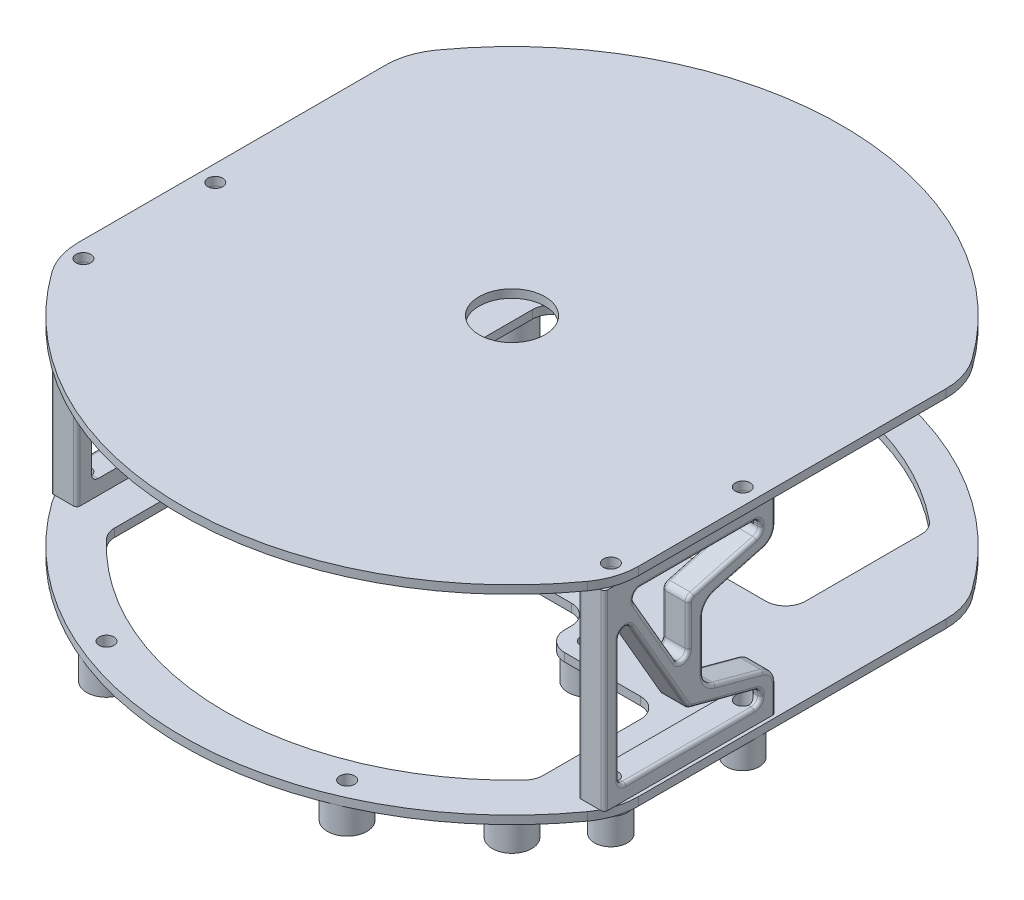
SolidWorks part; units mm, degrees
ref_plane "Front" through (0, 0, 0) normal (0, 0, 1) x (1, 0, 0)
ref_plane "Top" through (0, 0, 0) normal (0, 1, 0) x (1, 0, 0)
ref_plane "Right" through (0, 0, 0) normal (1, 0, 0) x (0, 0, -1)
sketch "Sketch1" plane through (0, 0, 0) normal (0, 1, 0) x (1, 0, 0)
  line L0 (0, 71.1393) -> (0, -87.7098) construction
  line L1 (-42.5, 26.3391) -> (-42.5, -26.3391)
  line L2 (42.5, 26.3391) -> (42.5, -26.3391)
  arc A0 (-42.5, -26.3391) -> (42.5, -26.3391) centre (0, 0) ccw
  arc A1 (42.5, 26.3391) -> (-42.5, 26.3391) centre (0, 0) ccw
  dimension "D1" = 100
  dimension "D2" = 85
extrude "Boss-Extrude1" add sketch "Sketch1" along normal blind 1.25
sketch "Sketch2" plane through (0, 0, 0) normal (0, -1, 0) x (1, 0, 0)
  line L0 (0, 45.5144) -> (0, -63.1722) construction
  line L1 (-51.2989, 0) -> (55.2567, 0) construction
  circle A0 centre (-33, 33) radius 3
  circle A2 centre (-33, 33) radius 1.125
  circle A4 centre (-33, -33) radius 1.125
  circle A5 centre (-33, -33) radius 3
  circle A6 centre (33, -33) radius 3
  circle A7 centre (33, -33) radius 1.125
  circle A8 centre (33, 33) radius 1.125
  circle A9 centre (33, 33) radius 3
  dimension "D3" = 2.25
  dimension "D4" = 6
  dimension "D1" = 66
  dimension "D2" = 66
extrude "Boss-Extrude2" add sketch "Sketch2" along normal blind 4
fillet "Fillet1" radius 10 4 edges at (-42.5, 0.625, -26.3391) (-42.5, 0.625, 26.3391) (42.5, 0.625, -26.3391) (42.5, 0.625, 26.3391)
sketch "Sketch3" plane through (0, 1.25, 0) normal (0, 1, 0) x (1, 0, 0)
  line L0 (0, 58.0627) -> (0, -62.1815) construction
  line L1 (-18.25, -6.75) -> (18.25, -6.75) construction
  line L2 (-18.25, -6.75) -> (-18.25, -43.25) construction
  line L3 (-18.25, -43.25) -> (18.25, -43.25) construction
  line L4 (18.25, -6.75) -> (18.25, -43.25) construction
  line L5 (-18.25, -6.75) -> (18.25, -43.25) construction
  line L6 (-18.25, -43.25) -> (18.25, -6.75) construction
  circle A0 centre (-18.25, -6.75) radius 1.125
  circle A1 centre (18.25, -6.75) radius 1.125
  circle A2 centre (18.25, -43.25) radius 1.125
  circle A3 centre (-18.25, -43.25) radius 1.125
  circle A4 centre (-40, -5) radius 1.125
  circle A5 centre (-40, -25) radius 1.125
  circle A6 centre (40, -25) radius 1.125
  circle A7 centre (40, -5) radius 1.125
  point P0 (0, -25)
  dimension "D1" = 2.25
  dimension "D2" = 36.5
  dimension "D3" = 25
  dimension "D4" = 20
  dimension "D5" = 80
  dimension "D6" = 0
sketch "Sketch4" plane through (0, 0, 0) normal (0, -1, 0) x (1, 0, 0)
  circle A0 centre (-18.25, 43.25) radius 3
  circle A1 centre (18.25, 43.25) radius 3
  circle A2 centre (18.25, 6.75) radius 3
  circle A3 centre (-18.25, 6.75) radius 3
  circle A4 centre (-40, 25) radius 2.5
  circle A5 centre (-40, 5) radius 2.5
  circle A6 centre (40, 25) radius 2.5
  circle A7 centre (40, 5) radius 2.5
  dimension "D1" = 6
  dimension "D2" = 5
extrude "Boss-Extrude3" add sketch "Sketch4" along normal up to surface (4 mm away) up to face at (-33, -4, 30)
extrude "Cut-Extrude1" cut sketch "Sketch3" against normal through all
sketch "Sketch6" plane through (0, 0, 0) normal (0, -1, 0) x (1, 0, 0)
  line L0 (-29.5, -33.9816) -> (-29.5, -12)
  line L1 (-29.5, -12) -> (-3.5, -12)
  line L2 (29.5, -12) -> (29.5, -33.9816)
  line L3 (0, 0) -> (0, -57.2909) construction
  line L4 (-32.5, 28.9137) -> (-32.5, 10)
  line L5 (-32.5, 10) -> (-15, 10)
  line L6 (32.5, 10) -> (32.5, 28.9137)
  line L7 (-3.5, -12) -> (-3.5, -44.8637)
  line L8 (3.5, -12) -> (3.5, -44.8637)
  line L9 (3.5, -12) -> (29.5, -12)
  line L10 (15, 10) -> (32.5, 10)
  line L12 (-15, 10) -> (-15, 3)
  line L13 (-15, 3) -> (15, 3)
  line L14 (15, 10) -> (15, 3)
  arc A0 (-29.5, -33.9816) -> (-3.5, -44.8637) centre (0, 0) ccw
  arc A1 (-40.625, -29.1481) -> (40.625, -29.1481) centre (0, 0) ccw construction
  arc A2 (-32.5, 28.9137) -> (32.5, 28.9137) centre (0, 0) cw
  arc A3 (40.625, 29.1481) -> (-40.625, 29.1481) centre (0, 0) ccw construction
  arc A4 (3.5, -44.8637) -> (29.5, -33.9816) centre (0, 0) ccw
  dimension "D2" = 5
  dimension "D4" = 6.5
  dimension "D1" = 59
  dimension "D3" = 12
  dimension "D5" = 10
  dimension "D6" = 7
  dimension "D7" = 65
  dimension "D8" = 7
  dimension "D9" = 30
extrude "Cut-Extrude2" cut sketch "Sketch6" against normal through all
fillet "Fillet2" radius 3 16 edges at (-29.5, 0.625, -12) (-3.5, 0.625, -12) (-3.5, 0.625, -44.8637) (29.5, 0.625, -12) (29.5, 0.625, -33.9816) (3.5, 0.625, -44.8637) (3.5, 0.625, -12) (-29.5, 0.625, -33.9816) (32.5, 0.625, 28.9137) (-32.5, 0.625, 28.9137) (-32.5, 0.625, 10) (32.5, 0.625, 10) (15, 0.625, 3) (15, 0.625, 10) (-15, 0.625, 3) (-15, 0.625, 10)
ref_point "Point1"
ref_plane "Plane1" through (-40, 0, 0) normal (-1, 0, 0) x (0, 0, 1)
sketch "Sketch7" plane through (-40, 0, 0) normal (-1, 0, 0) x (0, 0, 1)
  line L0 (2, 1.25) -> (2, 7.25)
  line L1 (-23.3184, 1.25) -> (23.3184, 1.25) construction
  line L2 (2, 7.25) -> (13, 10.1974)
  line L3 (13, 10.1974) -> (13, 21.3026)
  line L4 (13, 21.3026) -> (2, 24.25)
  line L5 (2, 24.25) -> (2, 30.25)
  line L6 (2, 30.25) -> (28, 30.25)
  line L7 (28, 30.25) -> (28, 1.25)
  line L8 (28, 1.25) -> (2, 1.25)
  line L9 (4.25, 28) -> (24.2157, 28)
  line L11 (25.75, 3.5) -> (4.25, 3.5)
  line L12 (4.25, 3.5) -> (4.25, 5.5235)
  line L13 (4.25, 5.5235) -> (15.25, 8.471)
  line L14 (15.25, 12.471) -> (15.25, 23.029)
  line L15 (15.25, 23.029) -> (4.25, 25.9765)
  line L16 (4.25, 25.9765) -> (4.25, 28)
  line L17 (15.25, 8.471) -> (25.75, 26.6575)
  line L19 (24.2157, 28) -> (15.25, 12.471)
  line L21 (15.25, 8.471) -> (15.25, 23.029) construction
  line L22 (25.75, 26.6575) -> (25.75, 3.5)
  line L23 (25.75, 28) -> (25.75, 3.5) construction
  line L24 (4.25, 28) -> (25.75, 28) construction
  dimension "D1" = 2
  dimension "D2" = 26
  dimension "D3" = 15
  dimension "D4" = 15
  dimension "D5" = 15
  dimension "D6" = 6
  dimension "D7" = 29
  dimension "D9" = 2
  dimension "D10" = 30
  dimension "D8" = 2.25
extrude "Boss-Extrude4" add sketch "Sketch7" along normal mid plane 4 separate body
fillet "Fillet3" radius 2.5 4 edges at (-40, 7.25, 2) (-40, 10.1974, 13) (-40, 21.3026, 13) (-40, 24.25, 2)
fillet "Fillet4" radius 1 10 edges at (-40, 26.6575, 25.75) (-40, 8.471, 15.25) (-40, 5.5235, 4.25) (-40, 3.5, 25.75) (-40, 3.5, 4.25) (-40, 12.471, 15.25) (-40, 28, 4.25) (-40, 25.9765, 4.25) (-40, 23.029, 15.25) (-40, 28, 24.2157)
fillet "Fillet5" radius 0.5 50 edges at (-38, 15.75, 28) (-38, 3.2908, 2) (-38, 6.8536, 2.5166) (-38, 8.7237, 7.5) (-38, 10.5939, 12.4834) (-38, 15.75, 13) (-38, 20.9061, 12.4834) (-38, 22.7763, 7.5) (-38, 24.6464, 2.5166) (-38, 28.2092, 2) (-42, 3.2908, 2) (-42, 6.8536, 2.5166) (-42, 8.7237, 7.5) (-42, 10.5939, 12.4834) (-42, 15.75, 13) (-42, 20.9061, 12.4834) (-42, 22.7763, 7.5) (-42, 24.6464, 2.5166) (-42, 28.2092, 2) (-42, 15.75, 28) (-42, 3.7929, 4.5429) (-42, 5.3649, 4.4566) (-42, 7.0429, 9.9205) (-42, 8.5363, 15.1998) (-42, 16.1276, 19.6705) (-42, 23.8914, 25.0088) (-42, 13.7127, 25.75) (-42, 3.7929, 25.4571) (-42, 3.5, 15) (-38, 27.7071, 4.5429) (-42, 27.7071, 4.5429) (-38, 26.1351, 4.4566) (-38, 24.5028, 9.75) (-38, 22.8705, 15.0434) (-38, 19.2324, 15.25) (-38, 15.2371, 15.9912) (-42, 26.1351, 4.4566) (-42, 24.5028, 9.75) (-42, 22.8705, 15.0434) (-42, 19.2324, 15.25) (-42, 15.2371, 15.9912) (-38, 28, 13.8668) (-42, 28, 13.8668) (-38, 21.1015, 20.2328) (-42, 21.1015, 20.2328) (-38, 27.5, 23.3497) (-42, 27.5, 23.3497) (-38, 26.8719, 4.25) (-42, 26.8719, 4.25) (-42, 4.6281, 4.25)
sketch "Sketch8" plane through (0, 1.25, 0) normal (0, -1, 0) x (1, 0, 0)
  circle A0 centre (-40, 5) radius 1.125 construction
  circle A1 centre (-40, 25) radius 1.125 construction
  circle A2 centre (-40, 5) radius 1.125
  circle A3 centre (-40, 25) radius 1.125
extrude "Cut-Extrude3" cut sketch "Sketch8" against normal blind 3.5
extrude "Cut-Extrude4" cut sketch "Sketch8<3>" along normal blind 3.5 from surface starting at face at (-40, 30.25, 15)
sketch "Sketch8<3>" plane through (0, 1.25, 0) normal (0, -1, 0) x (1, 0, 0) same geometry as "Sketch8"
mirror "Mirror1" about plane through (0, 0, 0) normal (1, 0, 0) of bodies 109
sketch "Sketch9" plane through (0, 30.25, 0) normal (0, 1, 0) x (1, 0, 0)
  line L0 (-42.5, 23.3184) -> (-42.5, -23.3184) construction
  line L1 (42.5, -23.3184) -> (42.5, 23.3184) construction
  line L2 (-42.5, 23.3184) -> (-42.5, -23.3184)
  line L3 (42.5, -23.3184) -> (42.5, 23.3184)
  arc A0 (40.625, 29.1481) -> (-40.625, 29.1481) centre (0, 0) ccw construction
  arc A1 (-40.625, 29.1481) -> (-42.5, 23.3184) centre (-32.5, 23.3184) ccw construction
  arc A2 (-42.5, -23.3184) -> (-40.625, -29.1481) centre (-32.5, -23.3184) ccw construction
  arc A3 (-40.625, -29.1481) -> (40.625, -29.1481) centre (0, 0) ccw construction
  arc A4 (40.625, -29.1481) -> (42.5, -23.3184) centre (32.5, -23.3184) ccw construction
  arc A5 (42.5, 23.3184) -> (40.625, 29.1481) centre (32.5, 23.3184) ccw construction
  arc A6 (-40.625, 29.1481) -> (-42.5, 23.3184) centre (-32.5, 23.3184) ccw
  arc A7 (-42.5, -23.3184) -> (-40.625, -29.1481) centre (-32.5, -23.3184) ccw
  arc A8 (-40.625, -29.1481) -> (40.625, -29.1481) centre (0, 0) ccw
  arc A9 (40.625, -29.1481) -> (42.5, -23.3184) centre (32.5, -23.3184) ccw
  arc A10 (42.5, 23.3184) -> (40.625, 29.1481) centre (32.5, 23.3184) ccw
  arc A11 (40.625, 29.1481) -> (-40.625, 29.1481) centre (0, 0) ccw
  circle A12 centre (0, 0) radius 5
  dimension "D1" = 10
extrude "Boss-Extrude6" add sketch "Sketch9" along normal blind 1.25 separate body
sketch "Sketch10" plane through (0, 30.25, 0) normal (0, -1, 0) x (1, 0, 0)
  line L0 (0, 53.912) -> (0, -58.3807) construction
  circle A0 centre (-40, 5) radius 1.125 construction
  circle A1 centre (-40, 25) radius 1.125 construction
  circle A2 centre (-40, 5) radius 1.125
  circle A3 centre (-40, 25) radius 1.125
  circle A4 centre (40, 25) radius 1.125
  circle A5 centre (40, 5) radius 1.125
extrude "Cut-Extrude5" cut sketch "Sketch10" against normal through all
equation "\"D5@Sketch7\"=\"D4@Sketch7\""
